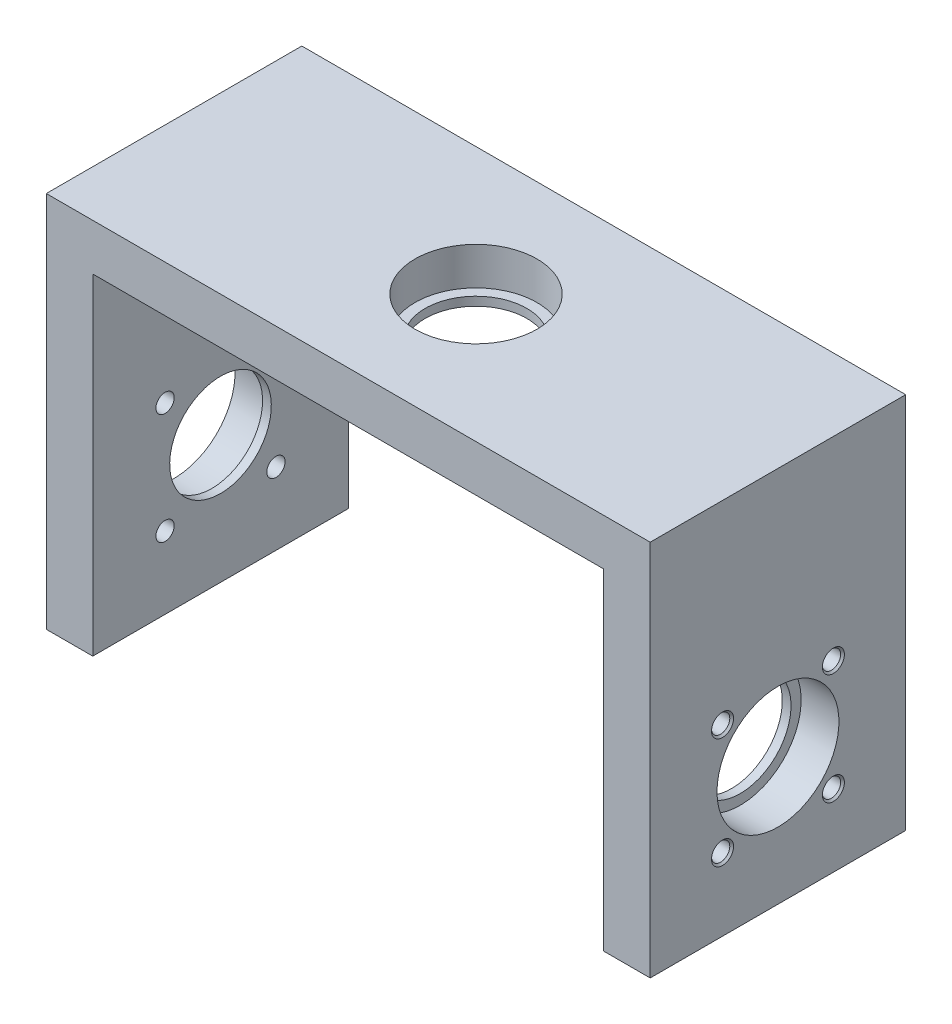
SolidWorks part; units mm, degrees
ref_plane "Front Plane" through (0, 0, 0) normal (0, 0, 1) x (1, 0, 0)
ref_plane "Top Plane" through (0, 0, 0) normal (0, 1, 0) x (1, 0, 0)
ref_plane "Right Plane" through (0, 0, 0) normal (1, 0, 0) x (0, 0, -1)
sketch "Sketch1" plane through (0, 0, 0) normal (0, 0, 1) x (1, 0, 0)
  line L0 (44, 0) -> (-44, 0)
  line L1 (-44, 0) -> (-44, -57)
  line L2 (-44, -57) -> (-52, -57)
  line L3 (-52, -57) -> (-52, 8)
  line L4 (-52, 8) -> (52, 8)
  line L5 (52, 8) -> (52, -57)
  line L6 (52, -57) -> (44, -57)
  line L7 (44, -57) -> (44, 0)
  point P4 (0, 0)
  dimension "D1" = 88
  dimension "D2" = 8
  dimension "D3" = 8
  dimension "D4" = 65
extrude "Boss-Extrude1" add sketch "Sketch1" along normal blind 44
sketch "Sketch4" plane through (-52, 0, 0) normal (-1, 0, 0) x (0, 0, 1)
  line L0 (0, -35) -> (22, -35) construction
  line L1 (0, 8) -> (0, -57) construction
  line L2 (22, -35) -> (44, -35) construction
  line L3 (44, 8) -> (44, -57) construction
  line L5 (44, -57) -> (0, -57) construction
  point P0 (22, -35)
  dimension "D1" = 22
hole_wizard "Ø21.0 (21) Diameter Hole1" positions "Sketch4" profile "Sketch3" hole size "Ø21.0" standard "DIN" end condition through all
sketch "Sketch3" plane through (-52, -35, 22) normal (0, 1, 0) x (0, 0, 1)
  line L0 (0, 0) -> (0, 104)
  line L1 (0, 104) -> (10.5, 104)
  line L2 (10.5, 104) -> (10.5, 0)
  line L5 (10.5, 0) -> (0, 0)
  line L11 (0, -6.35) -> (0, 107.95) construction
  dimension "Thru Hole Dia." = 21
  dimension "Thru Hole Depth" = 104
sketch "Sketch8" plane through (0, 8, 0) normal (0, 1, 0) x (1, 0, 0)
  line L0 (-52, -22) -> (0, -22) construction
  line L1 (-52, -44) -> (-52, 0) construction
  line L2 (0, -22) -> (52, -22) construction
  line L3 (52, -44) -> (52, 0) construction
  line L5 (0, 0) -> (0, -22) construction
  line L6 (0, -22) -> (0, -44) construction
  line L7 (52, -44) -> (-52, -44) construction
  point P2 (0, -22)
  point P23 (0, -22)
hole_wizard "Ø21.0 (21) Diameter Hole2" positions "Sketch8" profile "Sketch6" hole size "Ø21.0" standard "DIN" end condition through all
sketch "Sketch6" plane through (0, 8, 22) normal (1, 0, 0) x (0, 0, 1)
  line L0 (0, 0) -> (0, 65)
  line L1 (0, 65) -> (10.5, 65)
  line L2 (10.5, 65) -> (10.5, 0)
  line L5 (10.5, 0) -> (0, 0)
  line L11 (0, -6.35) -> (0, 107.95) construction
  dimension "Thru Hole Dia." = 21
  dimension "Thru Hole Depth" = 65
sketch "Sketch9" plane through (44, 0, 0) normal (-1, 0, 0) x (0, 0, 1)
  circle A0 centre (22, -35) radius 10.5 construction
  circle A1 centre (22, -35) radius 10.5
  circle A2 centre (22, -35) radius 8.75
  dimension "D1" = 1.75
extrude "Boss-Extrude2" add sketch "Sketch9" against normal blind 1.5
extrude "Boss-Extrude3" add sketch "Sketch9<2>" along normal blind 1.5 from surface starting at face at (-44, -45.5, 22)
sketch "Sketch9<2>" plane through (44, 0, 0) normal (-1, 0, 0) x (0, 0, 1) same geometry as "Sketch9"
sketch "Sketch12" plane through (-52, 0, 0) normal (-1, 0, 0) x (0, 0, 1)
  line L0 (31.5459, -25.4541) -> (22, -35)
  circle A0 centre (22, -35) radius 13.5
  point P5 (31.5459, -25.4541)
  point P17 (31.5459, -44.5459)
  point P18 (12.4541, -44.5459)
  point P19 (12.4541, -25.4541)
  point P21 (11.7196, -43.75)
  point P22 (0, 0)
  dimension "D1" = 27
  dimension "D2" = 45
  dimension "D3" = 4
hole_wizard "Tap Drill for M3 Helicoil2" positions "Sketch12" profile "Sketch11" hole size "M3x0.5" standard "DIN" end condition up to next
sketch "Sketch11" plane through (-52, -25.4541, 12.4541) normal (0, 1, 0) x (0, 0, 1)
  line L0 (0, 0) -> (0, 104)
  line L1 (0, 104) -> (1.575, 104)
  line L2 (1.575, 104) -> (1.575, 0.325)
  line L3 (1.575, 0.325) -> (1.9, 0)
  line L5 (1.9, 0) -> (0, 0)
  line L6 (-1.575, 0.325) -> (-1.9, 0) construction
  line L11 (0, -6.35) -> (0, 107.95) construction
  dimension "Thru Hole Dia." = 3.15
  dimension "Thru Hole Depth" = 104
  dimension "Near C'Sink Dia." = 3.8
  dimension "Near C'Sink Angle" = 90
sketch "Sketch15" plane through (52, 0, 0) normal (1, 0, 0) x (0, 0, -1)
  circle A7 centre (-12.4541, -44.5459) radius 1.575 construction
  circle A8 centre (-31.5459, -44.5459) radius 1.575 construction
  circle A9 centre (-31.5459, -25.4541) radius 1.575 construction
  circle A10 centre (-12.4541, -25.4541) radius 1.575 construction
  circle A11 centre (-12.4541, -44.5459) radius 1.575
  circle A12 centre (-31.5459, -44.5459) radius 1.575
  circle A13 centre (-31.5459, -25.4541) radius 1.575
  circle A14 centre (-12.4541, -25.4541) radius 1.575
  point P33 (-12.4541, -44.5459)
  point P35 (-31.5459, -44.5459)
  point P37 (-31.5459, -25.4541)
  point P39 (-12.4541, -25.4541)
hole_wizard "Tap Drill for M3 Helicoil2" positions "Sketch15" profile "Sketch14" hole size "M3x0.5" standard "DIN" end condition up to next
sketch "Sketch14" plane through (52, -44.5459, 12.4541) normal (0, 1, 0) x (0, 0, -1)
  line L0 (0, 0) -> (0, 8)
  line L1 (0, 8) -> (1.575, 8)
  line L2 (1.575, 8) -> (1.575, 0.325)
  line L3 (1.575, 0.325) -> (1.9, 0)
  line L5 (1.9, 0) -> (0, 0)
  line L6 (-1.575, 0.325) -> (-1.9, 0) construction
  line L11 (0, -6.35) -> (0, 107.95) construction
  dimension "Thru Hole Dia." = 3.15
  dimension "Thru Hole Depth" = 8
  dimension "Near C'Sink Dia." = 3.8
  dimension "Near C'Sink Angle" = 90
sketch "Sketch16" plane through (0, 0, 0) normal (0, 1, 0) x (1, 0, 0)
  circle A0 centre (0, -22) radius 10.5 construction
  circle A1 centre (0, -22) radius 10.5
  circle A2 centre (0, -22) radius 8.75
  dimension "D1" = 1.75
extrude "Boss-Extrude4" add sketch "Sketch16" along normal blind 1.5
